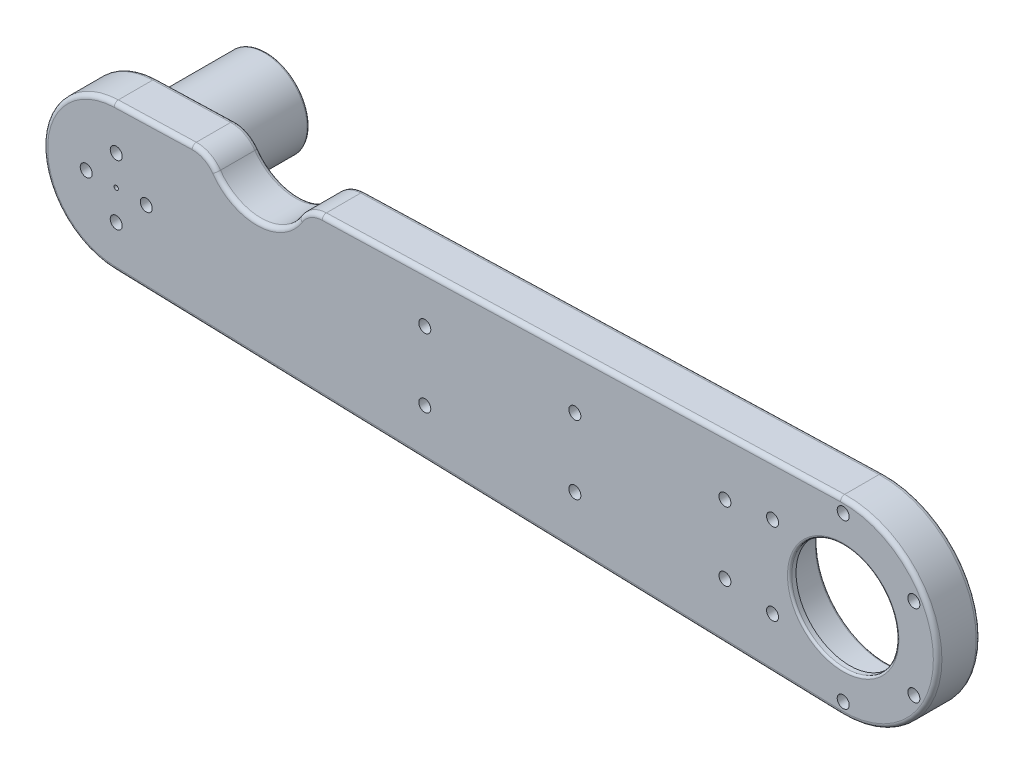
SolidWorks part; units mm, degrees
ref_plane "Front Plane" through (0, 0, 0) normal (0, 0, 1) x (1, 0, 0)
ref_plane "Top Plane" through (0, 0, 0) normal (0, 1, 0) x (1, 0, 0)
ref_plane "Right Plane" through (0, 0, 0) normal (1, 0, 0) x (0, 0, -1)
sketch "Sketch1" plane through (0, 0, 0) normal (0, 0, 1) x (1, 0, 0)
  line L4 (-84.77, 0) -> (84.77, 0) construction
  line L5 (-85.2739, 16.9925) -> (84.1172, 22.0153)
  line L6 (-85.2739, -16.9925) -> (84.1172, -22.0153)
  circle A2 centre (-84.77, 0) radius 12 construction
  circle A3 centre (84.77, 0) radius 16.025
  arc A4 (-85.2739, 16.9925) -> (-85.2739, -16.9925) centre (-84.77, 0) ccw
  arc A6 (84.1172, -22.0153) -> (84.1172, 22.0153) centre (84.77, 0) ccw
  circle A7 centre (-84.77, 0) radius 0.5
  dimension "D3" = 32.05
  dimension "D4" = 6
  dimension "D1" = 24
  dimension "D2" = 5
  dimension "D6" = 17
  dimension "D7" = 22.025
  dimension "D8" = 1
  dimension "D5" = 169.54
extrude "Boss-Extrude1" add sketch "Sketch1" along normal blind 5 and the other way blind 5
sketch "Sketch2" plane through (0, 0, 0) normal (0, 1, 0) x (1, 0, 0)
  line L0 (-84.27, 5) -> (-85.27, 5) construction
  line L1 (-84.27, 5) -> (-85.27, 5) construction
  line L2 (-84.77, 5) -> (-84.77, 30) construction
  line L3 (-84.77, 30) -> (-74.745, 30)
  line L4 (-74.745, 30) -> (-74.745, 7)
  line L5 (-74.745, 7) -> (-73.27, 7)
  line L6 (-73.27, 7) -> (-71.27, 5)
  line L7 (84.1172, 5) -> (-85.2739, 5) construction
  line L8 (-71.27, 5) -> (-84.77, 5)
  line L9 (-84.77, 5) -> (-84.77, 30)
  dimension "D1" = 20.05
  dimension "D2" = 23
  dimension "D3" = 45
  dimension "D4" = 2
  dimension "D5" = 23
revolve "Revolve1" add sketch "Sketch2" angle 360 about L9
sketch "Sketch3" plane through (0, 0, -30) normal (0, 0, -1) x (-1, 0, 0)
  line L0 (84.77, 7) -> (84.77, 0) construction
  circle A0 centre (84.77, 7) radius 1.4
  circle A1 centre (84.77, 7) radius 3.4 construction
  circle A2 centre (84.77, 0) radius 10.025 construction
  circle A3 centre (91.77, 0) radius 1.4
  circle A4 centre (84.77, -7) radius 1.4
  circle A5 centre (77.77, 0) radius 1.4
  point P15 (84.77, 0)
  dimension "D1" = 6.8
  dimension "D3" = 2.8
  dimension "D2" = 7
  dimension "D4" = 4
extrude "Cut-Extrude1" cut sketch "Sketch3" against normal through all
sketch "Sketch4" plane through (0, 0, -5) normal (0, 0, -1) x (-1, 0, 0)
  circle A0 centre (-84.77, 0) radius 19.025 construction
  circle A1 centre (-84.77, 19.025) radius 1.4
  circle A2 centre (-84.77, 19.025) radius 3 construction
  arc A3 (-84.1172, 22.0153) -> (-84.1172, -22.0153) centre (-84.77, 0) ccw construction
  circle A4 centre (-68.2939, 9.5125) radius 1.4
  circle A5 centre (-68.2939, -9.5125) radius 1.4
  circle A6 centre (-84.77, -19.025) radius 1.4
  circle A7 centre (-101.2461, -9.5125) radius 1.4
  circle A8 centre (-101.2461, 9.5125) radius 1.4
  circle A9 centre (-84.77, 19.025) radius 3.4 construction
  point P22 (-84.77, 0)
  dimension "D1" = 2.8
  dimension "D2" = 6
  dimension "D4" = 38.05
  dimension "D5" = 6.8
  dimension "D3" = 6
extrude "Cut-Extrude2" cut sketch "Sketch4" against normal through all
sketch "Sketch5" plane through (0, 0, 5) normal (0, 0, 1) x (1, 0, 0)
  circle A0 centre (84.77, 0) radius 12.5
  circle A1 centre (84.77, 0) radius 16.025 construction
  circle A2 centre (84.77, 0) radius 16.025
  dimension "D1" = 25
extrude "Boss-Extrude2" add sketch "Sketch5" against normal blind 1.5
sketch "Sketch6" plane through (0, 0, 5) normal (0, 0, 1) x (1, 0, 0)
  line L0 (84.1172, 22.0153) -> (-85.2739, 16.9925) construction
  line L1 (-67.0868, 17.5318) -> (-36.7576, 18.4311)
  line L2 (-42.2167, 15.2679) -> (-61.4499, 14.6976) construction
  arc A0 (-42.2167, 15.2679) -> (-61.4499, 14.6976) centre (-52.02, 21.28) cw
  arc A1 (-61.4499, 14.6976) -> (-67.0868, 17.5318) centre (-66.8902, 10.9001) ccw
  arc A2 (-42.2167, 15.2679) -> (-36.7576, 18.4311) centre (-36.5609, 11.7994) cw
  dimension "D1" = 3.3
  dimension "D3" = 32.75
  dimension "D4" = 11.5
  dimension "D2" = 3
extrude "FemurCutout" cut sketch "Sketch6" against normal through all
fillet "Fillet1" radius 1 16 edges at (-101.77, 0, 5) (-76.1803, 17.2622, 5) (23.6798, 20.2232, 5) (106.795, 0, 5) (106.795, 0, -5) (-0.5783, -19.5039, -5) (-101.77, 0, -5) (-0.5783, -19.5039, 5) (23.6798, 20.2232, -5) (-76.1803, 17.2622, -5) (-63.9099, 16.8277, 5) (-51.6792, 9.7851, 5) (-39.8872, 17.54, 5) (-63.9099, 16.8277, -5) (-51.6792, 9.7851, -5) (-39.8872, 17.54, -5)
fillet "Fillet2" radius 0.5 2 edges at (100.795, 0, -5) (-74.745, 0, -30)
fillet "Fillet3" radius 0.5 1 edges at (97.27, 0, 5)
sketch "Sketch9" plane through (0, 0, -5) normal (0, 0, -1) x (-1, 0, 0)
  circle A0 centre (-57.1852, -8) radius 1.6 construction
  circle A1 centre (-57.1852, 8) radius 1.6 construction
  circle A2 centre (-22.1852, -8) radius 1.6 construction
  circle A3 centre (-22.1852, 8) radius 1.6 construction
  circle A4 centre (12.8148, 8) radius 1.6 construction
  circle A5 centre (12.8148, -8) radius 1.6 construction
  circle A6 centre (-57.1852, -8) radius 1.6 construction
  circle A7 centre (-57.1852, 8) radius 1.6 construction
  circle A8 centre (-22.1852, -8) radius 1.6 construction
  circle A9 centre (-22.1852, 8) radius 1.6 construction
  circle A10 centre (12.8148, 8) radius 1.6 construction
  circle A11 centre (12.8148, -8) radius 1.6 construction
  circle A12 centre (-22.1852, -8) radius 1.4
  circle A13 centre (-22.1852, 8) radius 1.4
  circle A14 centre (-57.1852, 8) radius 1.4
  circle A15 centre (-57.1852, -8) radius 1.4
  circle A16 centre (12.8148, -8) radius 1.4
  circle A17 centre (12.8148, 8) radius 1.4
  dimension "D1" = 2.8
extrude "Cut-Extrude3" cut sketch "Sketch9" against normal through all
